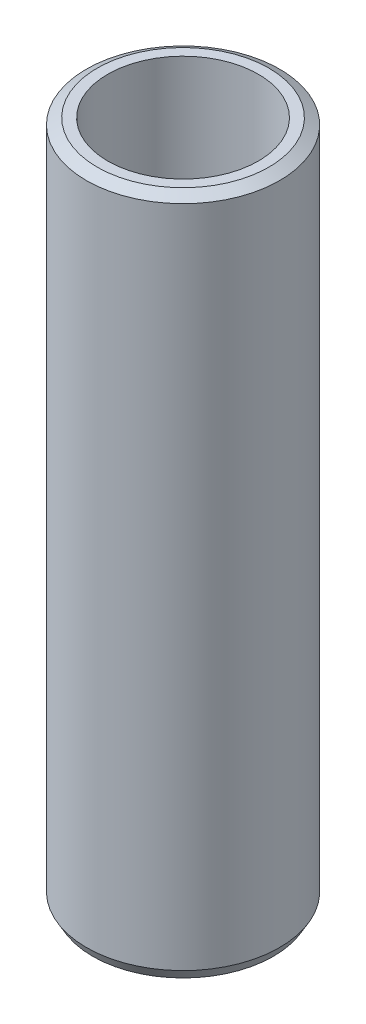
SolidWorks part; units mm, degrees
ref_plane "Front Plane" through (0, 0, 0) normal (0, 0, 1) x (1, 0, 0)
ref_plane "Top Plane" through (0, 0, 0) normal (0, 1, 0) x (1, 0, 0)
ref_plane "Right Plane" through (0, 0, 0) normal (1, 0, 0) x (0, 0, -1)
sketch "Sketch1" plane through (0, 0, 0) normal (0, 1, 0) x (1, 0, 0)
  circle A0 centre (0, 0) radius 57.5
  dimension "SHAFT_OD" = 115
extrude "Boss-Extrude1" add sketch "Sketch1" along normal blind 405.391
sketch "Sketch2" plane through (0, 0, 0) normal (0, 1, 0) x (1, 0, 0)
  circle A0 centre (0, 0) radius 44.8034
  dimension "BORE_D" = 89.6069
extrude "Cut-Extrude1" cut sketch "Sketch2" along normal through all
chamfer "Chamfer1" distance 3.7034 angle 60 2 edges at (0, 405.391, 57.5) (0, 0, 57.5) first distance on face at (0, 405.391, 57.5) first distance on face at (0, 0, 44.8034)
